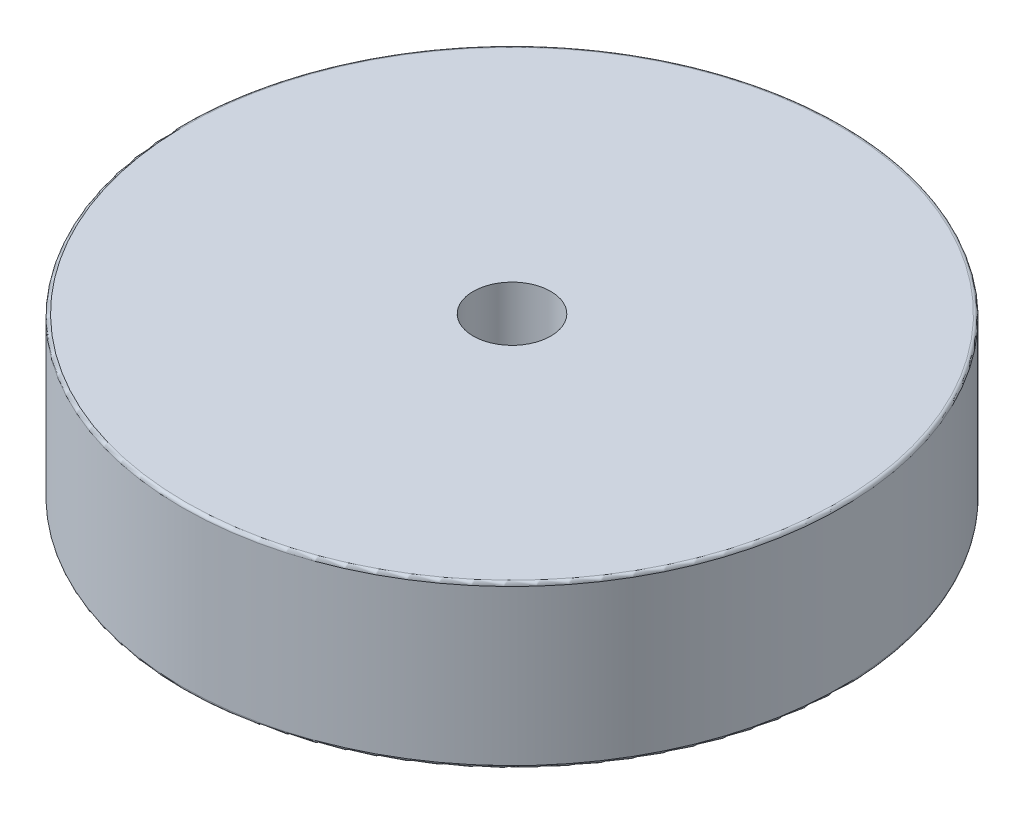
SolidWorks part; units mm, degrees
ref_plane "Front" through (0, 0, 0) normal (0, 0, 1) x (1, 0, 0)
ref_plane "Top" through (0, 0, 0) normal (0, 1, 0) x (1, 0, 0)
ref_plane "Right" through (0, 0, 0) normal (1, 0, 0) x (0, 0, -1)
sketch "Sketch2" plane through (0, 0, 0) normal (0, 1, 0) x (1, 0, 0)
  circle A0 centre (0, 0) radius 64.77
  dimension "D1" = 129.54
extrude "Boss-Extrude1" add sketch "Sketch2" along normal blind 31.75
fillet "Fillet1" radius 0.635 2 edges at (0, 0, 64.77) (0, 31.75, 64.77)
sketch "Sketch3" plane through (0, 31.75, 0) normal (0, 1, 0) x (1, 0, 0)
  circle A0 centre (0, 0) radius 7.62
  dimension "D1" = 15.24
extrude "Cut-Extrude1" cut sketch "Sketch3" against normal blind 13.97
